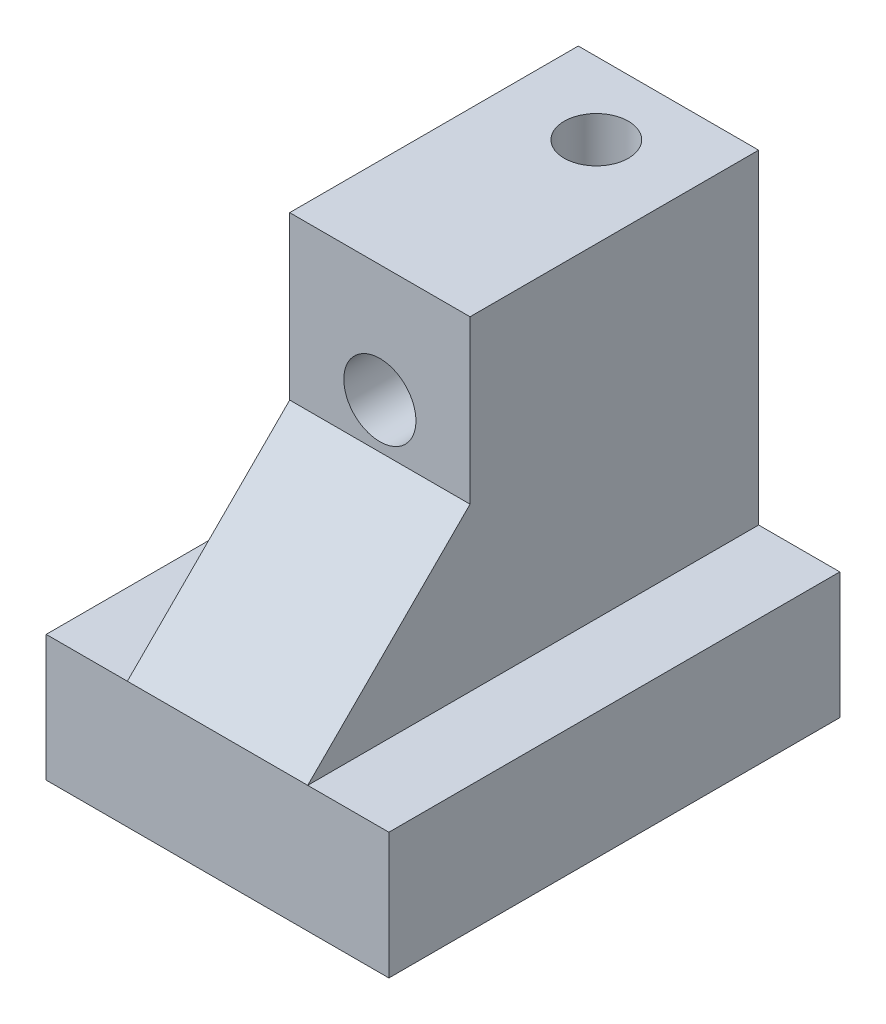
SolidWorks part; units mm, degrees
material "ABS PC"
ref_plane "Front Plane" through (0, 0, 0) normal (0, 0, 1) x (1, 0, 0)
ref_plane "Top Plane" through (0, 0, 0) normal (0, 1, 0) x (1, 0, 0)
ref_plane "Right Plane" through (0, 0, 0) normal (1, 0, 0) x (0, 0, -1)
sketch "Sketch1" plane through (0, 0, 0) normal (0, 0, 1) x (1, 0, 0)
  line L1 (-6.0325, -2.2225) -> (6.0325, -2.2225)
  line L2 (-6.0325, -2.2225) -> (-6.0325, 2.2225)
  line L3 (-6.0325, 2.2225) -> (6.0325, 2.2225)
  line L4 (6.0325, -2.2225) -> (6.0325, 2.2225)
  line L5 (-6.0325, -2.2225) -> (6.0325, 2.2225) construction
  line L6 (-6.0325, 2.2225) -> (6.0325, -2.2225) construction
  point P0 (0, 0)
  dimension "D1" = 12.065
  dimension "D2" = 4.445
extrude "Base" add sketch "Sketch1" along normal blind 15.875
sketch "Sketch7" plane through (0, 2.2225, 0) normal (0, 1, 0) x (1, 0, 0)
  line L1 (-3.175, -10.16) -> (3.175, -10.16)
  line L2 (-3.175, -10.16) -> (-3.175, 0)
  line L3 (-3.175, 0) -> (3.175, 0)
  line L4 (3.175, -10.16) -> (3.175, 0)
  line L15 (6.0325, 0) -> (-6.0325, 0) construction
  dimension "D1" = 6.35
  dimension "D2" = 10.16
extrude "Boss-Extrude1" add sketch "Sketch7" along normal blind 11.43
sketch "Sketch3" plane through (0, 0, 0) normal (0, 0, -1) x (-1, 0, 0)
  line L0 (6.0325, -2.2225) -> (-6.0325, -2.2225) construction
  circle A0 centre (0, 9.525) radius 1.27
  dimension "D1" = 2.54
  dimension "D2" = 11.7475
extrude "ShaftHole" cut sketch "Sketch3" against normal through all
hole_wizard "#4-40 Tapped Hole1" positions "Sketch9" profile "Sketch8" tap size "#4-40" standard "ANSI Inch" end condition up to next
sketch "Sketch9" plane through (0, 13.6525, 0) normal (0, 1, 0) x (1, 0, 0)
  line L3 (0, 0) -> (0, -5.08) construction
  line L4 (3.175, 0) -> (-3.175, 0) construction
  line L5 (0, -5.08) -> (0, -10.16) construction
  line L6 (-3.175, -10.16) -> (3.175, -10.16) construction
  point P2 (0, -2.54)
sketch "Sketch8" plane through (0, 13.6525, 2.54) normal (1, 0, 0) x (0, 0, 1)
  line L0 (0, 0) -> (0, 2.8575)
  line L1 (0, 2.8575) -> (1.1303, 2.8575)
  line L2 (1.1303, 2.8575) -> (1.1303, 0)
  line L5 (1.1303, 0) -> (0, 0)
  line L11 (0, -6.35) -> (0, 107.95) construction
  dimension "Thru Tap Drill Dia." = 2.2606
  dimension "Thru Tap Drill Depth" = 2.8575
cosmetic thread "Hole Thread1"
chamfer "Chamfer1" distance 5.715 angle 45 1 edges at (0, 2.2225, 10.16)
